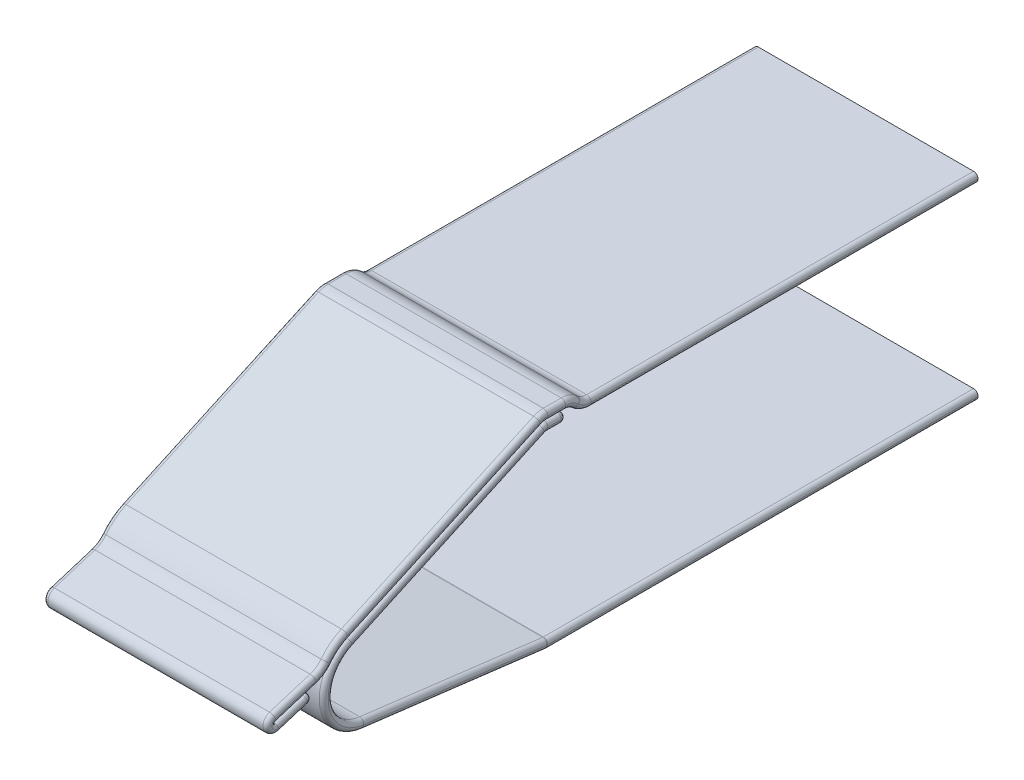
SolidWorks part; units mm, degrees
ref_plane "Front Plane" through (0, 0, 0) normal (0, 0, 1) x (1, 0, 0)
ref_plane "Top Plane" through (0, 0, 0) normal (0, 1, 0) x (1, 0, 0)
ref_plane "Right Plane" through (0, 0, 0) normal (1, 0, 0) x (0, 0, -1)
sketch "Sketch1" plane through (0, 0, 0) normal (1, 0, 0) x (0, 0, -1)
  line L0 (0, 0) -> (-48, 0)
  line L1 (-69.8723, 11.092) -> (-48.4161, 20.9093)
  line L2 (-46, 22.1) -> (-48, 22.1)
  line L3 (-48.8737, 21.9096) -> (-70.33, 12.0923)
  line L4 (-48, 21) -> (-46, 21)
  line L5 (-43.1663, 21) -> (0, 21)
  line L6 (-48.1227, 0.0076) -> (-68.5523, 2.534)
  line L7 (-73.8726, 9.4439) -> (-78.3968, 8.0312)
  line L8 (-78.0689, 6.9812) -> (-74.3719, 8.1356)
  arc A0 (-68.5523, 2.534) -> (-69.8723, 11.092) centre (-68, 7) cw
  arc A1 (-70.33, 12.0923) -> (-72.4063, 10.4561) centre (-68, 7) ccw
  arc A2 (-48.4161, 20.9093) -> (-48, 21) centre (-48, 20) cw
  arc A3 (-48, 22.1) -> (-48.8737, 21.9096) centre (-48, 20) ccw
  arc A4 (-46, 22.1) -> (-44.5831, 21.55) centre (-46, 20) cw
  arc A5 (-44.5831, 21.55) -> (-43.1663, 21) centre (-43.1663, 23.1) ccw
  arc A6 (-48, 0) -> (-48.1227, 0.0076) centre (-48, 1) cw
  arc A7 (-72.4063, 10.4561) -> (-73.8726, 9.4439) centre (-74.7668, 12.3076) cw
  arc A8 (-78.3968, 8.0312) -> (-78.0689, 6.9812) centre (-78.2329, 7.5062) ccw
  point P25 (-48.0616, 0)
  dimension "D4" = 1
  dimension "D5" = 48
  dimension "D7" = 1
  dimension "D3" = 4.5
  dimension "D10" = 3
  dimension "D1" = 1.1
  dimension "D2" = 21
  dimension "D6" = 2
  dimension "D8" = 7
  dimension "D9" = 68
  dimension "D11" = 1.1
extrude "Extrude-Thin1" add sketch "Sketch1" along normal mid plane 25 thin thin type mid plane wall 1
fillet "Fillet1" radius 0.5 48 edges at (12.5, 11.0057, 71.1566) (-12.5, 11.0057, 71.1566) (12.5, 16.5463, 59.3938) (-12.5, 16.5463, 59.3938) (12.5, 17.4556, 59.8099) (-12.5, 17.4556, 59.8099) (12.5, 21.6, 47) (-12.5, 21.6, 47) (12.5, 11.7912, 71.7755) (-12.5, 11.7912, 71.7755) (12.5, 8.1356, 74.3719) (-12.5, 8.1356, 74.3719) (12.5, 20.5, 21.5831) (12.5, 20.6762, 44.1071) (12.5, 21.4916, 45.421) (12.5, 21.5633, 48.3407) (-12.5, 20.5, 21.5831) (-12.5, 20.6762, 44.1071) (-12.5, 21.4916, 45.421) (-12.5, 21.5633, 48.3407) (12.5, 21.5, 21.5831) (12.5, 21.6084, 43.7453) (12.5, 22.4238, 45.0591) (12.5, 22.6, 47) (12.5, 22.5404, 48.5536) (-12.5, 21.5, 21.5831) (-12.5, 21.6084, 43.7453) (-12.5, 22.4238, 45.0591) (-12.5, 22.6, 47) (-12.5, 22.5404, 48.5536) (12.5, 8.2603, 75.9857) (12.5, 9.4272, 72.7785) (-12.5, 8.2603, 75.9857) (-12.5, 9.4272, 72.7785) (12.5, 9.2148, 76.2837) (12.5, 10.2501, 73.3466) (-12.5, 9.2148, 76.2837) (-12.5, 10.2501, 73.3466) (12.5, 8.0357, 76.3694) (12.5, 7.4913, 78.2806) (-12.5, 8.0357, 76.3694) (-12.5, 7.4913, 78.2806) (12.5, 7.0811, 76.0714) (12.5, 7.1932, 79.2352) (-12.5, 7.0811, 76.0714) (-12.5, 7.1932, 79.2352) (0, 7.6584, 74.2228) (0, 8.6129, 74.5209)
fillet "Fillet2" radius 0.5 32 edges at (12.5, 0.5, 24) (12.5, 15.546, 58.9362) (-12.5, 0.5, 24) (-12.5, 15.546, 58.9362) (12.5, -0.5, 24) (12.5, 16.4553, 59.3522) (-12.5, -0.5, 24) (-12.5, 16.4553, 59.3522) (12.5, 6.3902, 71.9533) (-12.5, 6.3902, 71.9533) (12.5, 6.2378, 72.9416) (-12.5, 6.2378, 72.9416) (12.5, 21, 46) (-12.5, 21, 46) (12.5, 20.5, 47) (12.5, 20.4885, 48.1065) (-12.5, 20.5, 47) (-12.5, 20.4885, 48.1065) (12.5, 21.5, 47) (12.5, 21.4656, 48.3194) (-12.5, 21.5, 47) (-12.5, 21.4656, 48.3194) (0, 20.5, 46) (0, 21.5, 46) (12.5, 0.5009, 48.0307) (12.5, 1.767, 58.2761) (-12.5, 0.5009, 48.0307) (-12.5, 1.767, 58.2761) (12.5, -0.4972, 48.0922) (12.5, 0.7746, 58.3989) (-12.5, -0.4972, 48.0922) (-12.5, 0.7746, 58.3989)
